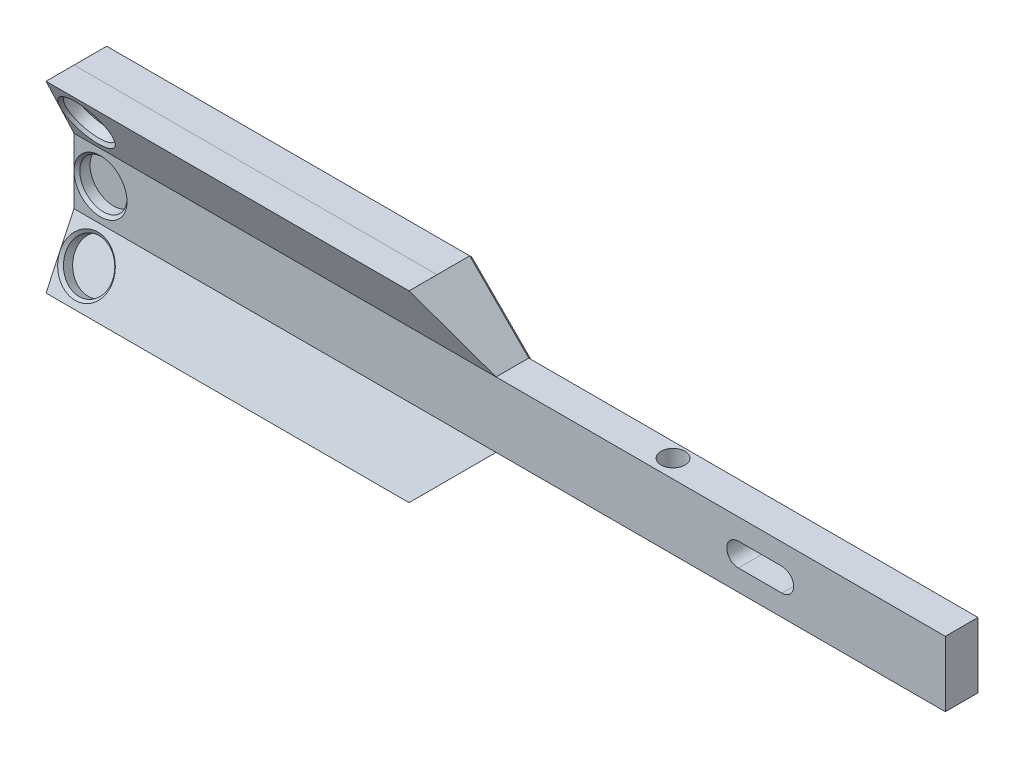
SolidWorks part; units mm, degrees
ref_plane "Front" through (0, 0, 0) normal (0, 0, 1) x (1, 0, 0)
ref_plane "Top" through (0, 0, 0) normal (0, 1, 0) x (1, 0, 0)
ref_plane "Right" through (0, 0, 0) normal (1, 0, 0) x (0, 0, -1)
sketch "Sketch1" plane through (0, 0, 0) normal (0, 0, 1) x (1, 0, 0)
  line L1 (60, -4.5) -> (-60, -4.5)
  line L2 (60, -4.5) -> (60, 4.5)
  line L3 (60, 4.5) -> (-60, 4.5)
  line L4 (-60, -4.5) -> (-60, 4.5)
  line L5 (60, -4.5) -> (-60, 4.5) construction
  line L6 (60, 4.5) -> (-60, -4.5) construction
  point P0 (0, 0)
  dimension "D1" = 9
  dimension "D2" = 120
extrude "Boss-Extrude1" add sketch "Sketch1" along normal blind 5
sketch "Sketch2" plane through (0, 4.5, 0) normal (0, 1, 0) x (1, 0, 0)
  line L0 (60, -5) -> (60, 0) construction
  line L2 (60, 0) -> (-60, 0) construction
  circle A0 centre (20, -2.5) radius 1.65
  dimension "D3" = 3.3
  dimension "D1" = 2.5
  dimension "D2" = 40
sketch "Sketch4" plane through (0, 0, 5) normal (0, 0, 1) x (1, 0, 0)
  line L0 (31.5, 0) -> (37.5, 0) construction
  line L1 (31.5, 1.6) -> (37.5, 1.6)
  line L2 (31.5, -1.6) -> (37.5, -1.6)
  arc A0 (31.5, 1.6) -> (31.5, -1.6) centre (31.5, 0) ccw
  arc A1 (37.5, -1.6) -> (37.5, 1.6) centre (37.5, 0) ccw
  point P2 (34.5, 0)
  dimension "D1" = 1.6
  dimension "D2" = 34.5
  dimension "D3" = 6
extrude "Cut-Extrude1" cut sketch "Sketch4" against normal blind 5
sketch "Sketch8" plane through (0, 0, 0) normal (0, 0, -1) x (-1, 0, 0)
  line L0 (60, 4.5) -> (60, -4.5) construction
  line L1 (60, 12.63) -> (10, 12.63)
  line L2 (60, 12.63) -> (60, -12.63)
  line L3 (60, -12.63) -> (10, -12.63)
  line L4 (10, 12.63) -> (10, -12.63)
  line L6 (-60, 4.5) -> (60, 4.5) construction
  dimension "D1" = 25.26
  dimension "D2" = 8.13
  dimension "D3" = 50
extrude "Boss-Extrude3" add sketch "Sketch8" against normal up to surface (5 mm away) up to face at (34.5, 0, 5)
sketch "Sketch9" plane through (-60, 0, 0) normal (-1, 0, 0) x (0, 0, 1)
  line L0 (5, 12.63) -> (5, -12.63) construction
  line L1 (5, 12.6327) -> (8.8548, 12.6327)
  line L2 (8.8548, 12.6327) -> (5, 4.5)
  line L3 (5, 4.5) -> (5, 12.6327)
  line L4 (-3.9634, 0) -> (12.9509, 0) construction
  line L5 (8.8548, -12.6327) -> (5, -4.5)
  line L6 (5, -12.6327) -> (8.8548, -12.6327)
  line L7 (5, -4.5) -> (5, -12.6327)
  circle A0 centre (25, 0) radius 20 construction
  dimension "D1" = 40
  dimension "D2" = 9
  dimension "D3" = 9
extrude "Boss-Extrude4" add sketch "Sketch9" against normal up to surface (50 mm away) up to face at (-10, 8.565, 2.5)
chamfer "Chamfer4" distance 8.13 2 edges at (-10, 4.5, 2.5) (-10, -4.5, 2.5)
chamfer "Chamfer1" distance 0.5 angle 45 12 edges at (60, 0, 0) (29.065, 4.5, 0) (-60, 0, 0) (29.065, -4.5, 0) (39.1, 0, 0) (34.5, -1.6, 0) (29.9, 0, 0) (34.5, 1.6, 0) (-35, 12.63, 0) (-35, -12.63, 0) (-5.935, 8.565, 0) (-5.935, -8.565, 0)
sketch "Sketch10" plane through (-60, 0, 0) normal (-1, 0, 0) x (0, 0, 1)
  line L0 (5, 4.5) -> (5, -4.5) construction
  line L1 (5, 4.5) -> (8.8548, 12.6327) construction
  line L2 (8.8548, -12.6327) -> (5, -4.5) construction
  circle A0 centre (25, 0) radius 20
sketch "Sketch11" plane through (0, 0, 5) normal (0, 0, 1) x (1, 0, 0)
  line L2 (-60, 4.5) -> (-60, -4.5) construction
  circle A0 centre (-56.35, 0) radius 3.25
  dimension "D1" = 6.5
  dimension "D2" = 3.65
extrude "Cut-Extrude3" cut sketch "Sketch11" against normal blind 1.8
sketch "Sketch12" plane through (0, -1.1096, 2.341) normal (0, -0.4283, 0.9036) x (1, 0, 0)
  line L1 (-10, 15.2079) -> (-60, 15.2079) construction
  line L2 (-60, 30.7079) -> (-60, -9.2921) construction
  circle A0 centre (-56.35, 10.7079) radius 3.25
  dimension "D1" = 6.5
  dimension "D2" = 4.5
  dimension "D3" = 3.65
extrude "Cut-Extrude4" cut sketch "Sketch12" against normal blind 1.8
mirror "Mirror2" about plane through (0, 0, 0) normal (0, 1, 0) of "Cut-Extrude4"
chamfer "Chamfer2" distance 0.4 angle 45 3 edges at (-53.1, 0, 5) (-56.35, -5.6295, 5.5354) (-56.35, 5.6295, 5.5354)
ref_plane "Plane1" through (-56, 0, 0) normal (-1, 0, 0) x (0, 0, 1)
extrude "Cut-Extrude5" cut sketch "Sketch2" against normal blind 10
